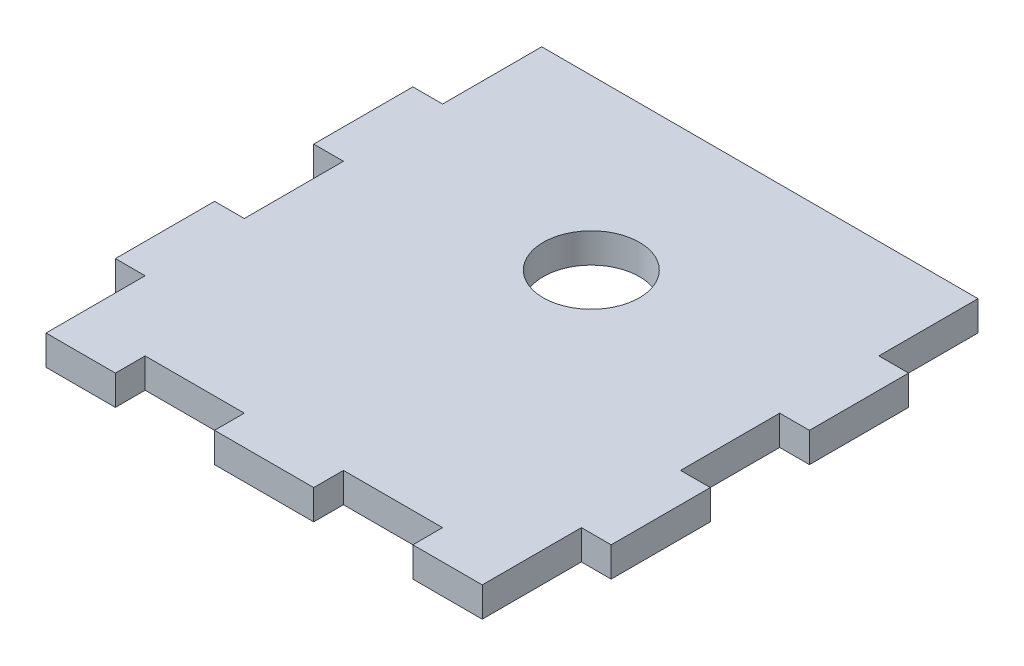
SolidWorks part; units mm, degrees
ref_plane "Alzado" through (0, 0, 0) normal (0, 0, 1) x (1, 0, 0)
ref_plane "Planta" through (0, 0, 0) normal (0, 1, 0) x (1, 0, 0)
ref_plane "Vista lateral" through (0, 0, 0) normal (1, 0, 0) x (0, 0, -1)
sketch "Croquis1" plane through (0, 0, 0) normal (0, 1, 0) x (1, 0, 0)
  line L0 (3, 0) -> (10, 0)
  line L1 (50, 10) -> (50, 20)
  line L2 (47, 50) -> (3, 50)
  line L3 (0, 40) -> (0, 30)
  line L4 (25, 0) -> (20, 0)
  line L5 (20, 0) -> (20, 3)
  line L6 (20, 3) -> (10, 3)
  line L7 (10, 3) -> (10, 0)
  line L8 (50, 30) -> (50, 40)
  line L9 (40, 3) -> (40, 0)
  line L10 (30, 0) -> (30, 3)
  line L11 (30, 3) -> (40, 3)
  line L12 (0, 20) -> (0, 10)
  line L13 (47, 20) -> (47, 30)
  line L14 (47, 30) -> (50, 30)
  line L15 (50, 30) -> (50, 40)
  line L16 (50, 40) -> (47, 40)
  line L17 (47, 40) -> (47, 50)
  line L18 (47, 10) -> (47, 0)
  line L19 (50, 10) -> (47, 10)
  line L20 (47, 20) -> (50, 20)
  line L21 (3, 20) -> (0, 20)
  line L22 (0, 10) -> (3, 10)
  line L23 (3, 10) -> (3, 0)
  line L24 (3, 40) -> (3, 50)
  line L25 (0, 40) -> (3, 40)
  line L26 (3, 30) -> (0, 30)
  line L27 (3, 20) -> (3, 30)
  line L28 (20, 0) -> (30, 0)
  line L29 (40, 0) -> (47, 0)
  circle A0 centre (25, 33) radius 4.85
  dimension "D7" = 9.7
  dimension "D3" = 5
  dimension "D4" = 3
  dimension "D5" = 10
  dimension "D6" = 33
  dimension "D10" = 10
extrude "Saliente-Extruir1" add sketch "Croquis1" along normal blind 3 contours L9 L29 L18 L19 L1 L20 L13 L14 L8 L16 L17 L2 L24 L25 L3 L26 L27 L21 L12 L22 L23 L0 L7 L6 L5 L4 L28 L10 L11 A0 region at (25, 0, -25.3746)
